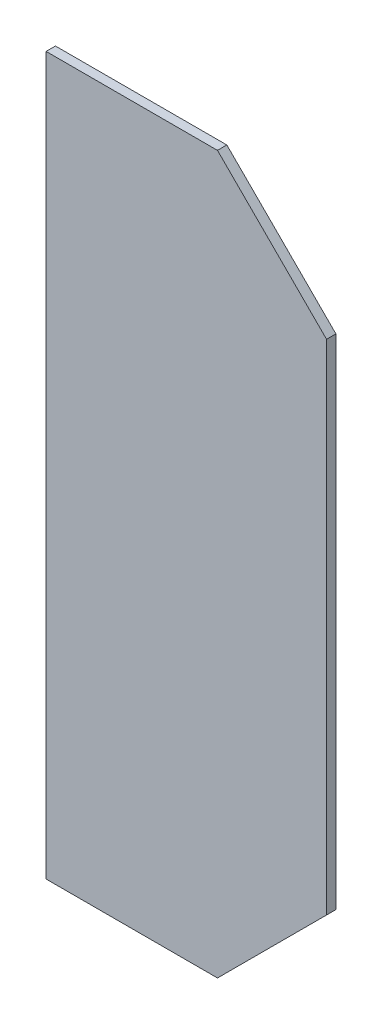
SolidWorks part; units mm, degrees
ref_plane "Front Plane" through (0, 0, 0) normal (0, 0, 1) x (1, 0, 0)
ref_plane "Top Plane" through (0, 0, 0) normal (0, 1, 0) x (1, 0, 0)
ref_plane "Right Plane" through (0, 0, 0) normal (1, 0, 0) x (0, 0, -1)
sketch "Sketch1" plane through (0, 0, 0) normal (0, 0, 1) x (1, 0, 0)
  line L1 (-45, 115) -> (45, 115)
  line L2 (-45, 115) -> (-45, -115)
  line L3 (-45, -115) -> (45, -115)
  line L4 (45, 115) -> (45, -115)
  line L5 (-45, 115) -> (45, -115) construction
  line L6 (-45, -115) -> (45, 115) construction
  point P0 (0, 0)
  dimension "D1" = 230
  dimension "D2" = 90
extrude "Boss-Extrude1" add sketch "Sketch1" along normal blind 3
chamfer "Chamfer2" distance 35 angle 45 2 edges at (45, -115, 1.5) (45, 115, 1.5)
